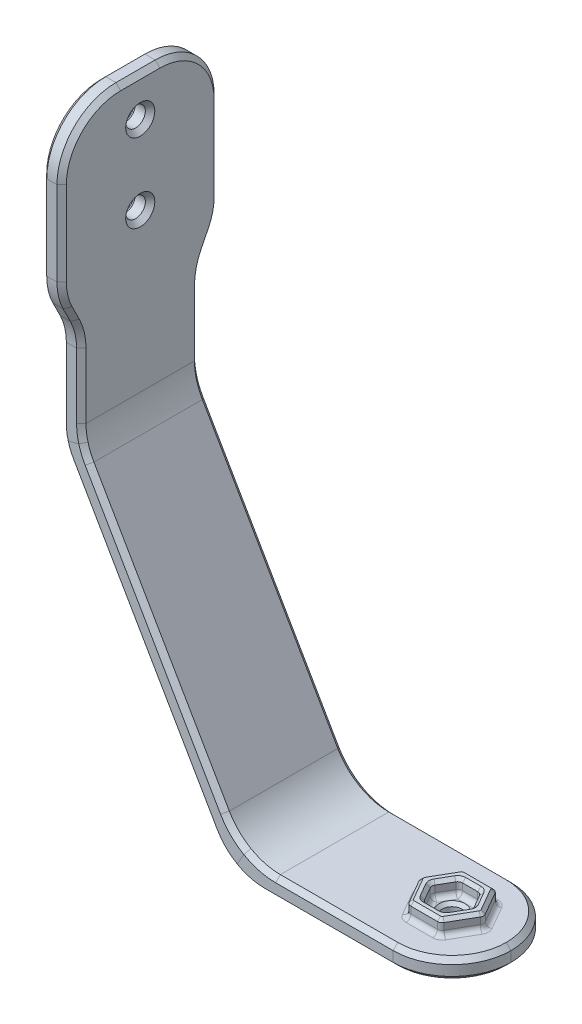
SolidWorks part; units mm, degrees
material "Onyx"
ref_plane "Front Plane" through (0, 0, 0) normal (0, 0, 1) x (1, 0, 0)
ref_plane "Top Plane" through (0, 0, 0) normal (0, 1, 0) x (1, 0, 0)
ref_plane "Right Plane" through (0, 0, 0) normal (1, 0, 0) x (0, 0, -1)
sketch "Sketch1" plane through (0, 0, 0) normal (0, 0, 1) x (1, 0, 0)
  line L0 (0, 0) -> (0, -47.5145)
  line L1 (0, -47.5145) -> (26.5798, -93.552)
  line L2 (26.5798, -93.552) -> (61.5048, -93.552)
  dimension "D1" = 47.5145
  dimension "D3" = 150
  dimension "D4" = 120
  dimension "D5" = 34.925
  dimension "D2" = 46.0375
sketch "Sketch2" plane through (0, 0, 0) normal (0, 1, 0) x (1, 0, 0)
  line L1 (-1.5875, -9.525) -> (1.5875, -9.525)
  line L2 (-1.5875, -9.525) -> (-1.5875, 9.525)
  line L3 (-1.5875, 9.525) -> (1.5875, 9.525)
  line L4 (1.5875, -9.525) -> (1.5875, 9.525)
  line L5 (-1.5875, -9.525) -> (1.5875, 9.525) construction
  line L6 (-1.5875, 9.525) -> (1.5875, -9.525) construction
  point P0 (0, 0)
  dimension "D1" = 3.175
  dimension "D2" = 19.05
sweep "Sweep1" add profiles "Sketch2" path "Sketch1"
sketch "Sketch7" plane through (0, 0, 0) normal (1, 0, 0) x (0, 0, -1)
  line L0 (-12.7, -25.4) -> (-9.525, -31.75)
  line L1 (-12.7, 0) -> (12.7, 0)
  line L2 (-12.7, 0) -> (-12.7, -25.4)
  line L3 (-12.7, -25.4) -> (12.7, -25.4) construction
  line L4 (12.7, 0) -> (12.7, -25.4)
  line L5 (-9.525, 0) -> (-9.525, -47.0892) construction
  line L6 (-9.525, -31.75) -> (9.525, -31.75)
  line L7 (9.525, 0) -> (9.525, -47.0892) construction
  line L8 (9.525, -31.75) -> (12.7, -25.4)
  dimension "D1" = 25.4
  dimension "D2" = 25.4
  dimension "D3" = 6.35
extrude "Boss-Extrude1" add sketch "Sketch7" along normal mid plane 3.175 contours L2 L0 L6 L8 L4 L1
sketch "Sketch8" plane through (0, 0, 0) normal (1, 0, 0) x (0, 0, -1)
  line L0 (0, -19.05) -> (0, -6.35) construction
  line L1 (0, -6.35) -> (0, 0) construction
  circle A0 centre (0, -6.35) radius 1.5875
  circle A1 centre (0, -19.05) radius 1.5875
  dimension "D1" = 3.175
  dimension "D2" = 6.35
  dimension "D3" = 12.7
extrude "Cut-Extrude1" cut sketch "Sketch8" against normal through all both and the other way through all
sketch "Sketch9" plane through (0, -91.9645, 0) normal (0, 1, 0) x (1, 0, 0)
  line L0 (61.5048, 0) -> (51.9798, 0) construction
  line L1 (61.5048, -9.525) -> (61.5048, 9.525) construction
  circle A0 centre (51.9798, 0) radius 1.5875
  dimension "D1" = 3.175
  dimension "D2" = 9.525
extrude "Cut-Extrude2" cut sketch "Sketch9" against normal through all both and the other way through all
sketch "Sketch10" plane through (0, -91.9645, 0) normal (0, 1, 0) x (1, 0, 0)
  line L1 (53.6662, 2.921) -> (50.2933, 2.921)
  line L2 (50.2933, 2.921) -> (48.6069, 0)
  line L3 (48.6069, 0) -> (50.2933, -2.921)
  line L4 (50.2933, -2.921) -> (53.6662, -2.921)
  line L5 (53.6662, -2.921) -> (55.3526, 0)
  line L6 (55.3526, 0) -> (53.6662, 2.921)
  line L7 (54.5827, 4.5085) -> (49.3768, 4.5085)
  line L8 (49.3768, 4.5085) -> (46.7738, 0)
  line L9 (46.7738, 0) -> (49.3768, -4.5085)
  line L10 (49.3768, -4.5085) -> (54.5827, -4.5085)
  line L11 (54.5827, -4.5085) -> (57.1857, 0)
  line L12 (57.1857, 0) -> (54.5827, 4.5085)
  circle A0 centre (51.9798, 0) radius 2.921 construction
  circle A1 centre (51.9798, 0) radius 4.5085 construction
  dimension "D1" = 5.842
  dimension "D2" = 1.5875
extrude "Boss-Extrude2" add sketch "Sketch10" along normal blind 2.3813
fillet "Fillet1" radius 9.525 12 edges at (0, -31.75, -9.525) (0, -25.4, -12.7) (0, -31.75, 9.525) (0, -25.4, 12.7) (0, 0, -12.7) (0, 0, 12.7) (61.5048, -93.552, -9.525) (61.5048, -93.552, 9.525) (1.5875, -47.0892, 0) (-1.5875, -47.9399, 0) (25.6632, -95.1395, 0) (27.4963, -91.9645, 0)
fillet "Fillet2" radius 0.7937 24 edges at (57.1857, -90.7739, 0) (54.5827, -90.7739, 4.5085) (46.7738, -90.7739, 0) (49.3768, -90.7739, -4.5085) (54.5827, -90.7739, -4.5085) (49.3768, -90.7739, 4.5085) (48.6069, -90.7739, 0) (50.2933, -90.7739, 2.921) (53.6662, -90.7739, 2.921) (55.3526, -90.7739, 0) (53.6662, -90.7739, -2.921) (50.2933, -90.7739, -2.921) (51.9798, -91.9645, 2.921) (49.4501, -91.9645, 1.4605) (49.4501, -91.9645, -1.4605) (54.5094, -91.9645, -1.4605) (54.5094, -91.9645, 1.4605) (51.9798, -91.9645, -2.921) (51.9798, -91.9645, -4.5085) (48.0753, -91.9645, -2.2543) (48.0753, -91.9645, 2.2543) (51.9798, -91.9645, 4.5085) (55.8842, -91.9645, -2.2543) (55.8842, -91.9645, 2.2542)
chamfer "Chamfer1" distance 0.762 angle 45 58 edges at (58.715, -95.1395, 6.7352) (58.715, -95.1395, -6.7352) (41.5711, -95.1395, 9.525) (41.5711, -95.1395, -9.525) (28.6972, -94.815, 9.525) (28.6972, -94.815, -9.525) (24.4273, -92.3497, 9.525) (24.4273, -92.3497, -9.525) (11.3011, -70.2636, 9.525) (11.3011, -70.2636, -9.525) (-0.8625, -49.0327, 9.525) (-0.8625, -49.0327, -9.525) (-1.506, -46.631, 9.525) (-1.506, -46.631, -9.525) (-1.5875, -39.6931, 9.525) (-1.5875, -31.8102, 9.7798) (-1.5875, -28.575, 11.1125) (-1.5875, -25.3398, 12.4452) (-1.5875, -16.3382, 12.7) (-1.5875, -2.7898, 9.9102) (-1.5875, 0, 0) (-1.5875, -2.7898, -9.9102) (-1.5875, -16.3382, -12.7) (-1.5875, -25.3398, -12.4452) (-1.5875, -28.575, -11.1125) (-1.5875, -31.8102, -9.7798) (-1.5875, -39.6931, -9.525) (-1.5875, -19.05, -1.5875) (-1.5875, -6.35, -1.5875) (58.715, -91.9645, -6.7352) (58.715, -91.9645, 6.7352) (42.4877, -91.9645, -9.525) (42.4877, -91.9645, 9.525) (30.5303, -91.64, -9.525) (30.5303, -91.64, 9.525) (26.2604, -89.1747, -9.525) (26.2604, -89.1747, 9.525) (13.8051, -68.2507, -9.525) (13.8051, -68.2507, 9.525) (2.3125, -48.182, -9.525) (2.3125, -48.182, 9.525) (1.669, -45.7802, -9.525) (1.669, -45.7802, 9.525) (1.5875, -39.2677, -9.525) (1.5875, -31.8102, -9.7798) (1.5875, -28.575, -11.1125) (1.5875, -25.3398, -12.4452) (1.5875, -16.3382, -12.7) (1.5875, -2.7898, -9.9102) (1.5875, 0, 0) (1.5875, -2.7898, 9.9102) (1.5875, -16.3382, 12.7) (1.5875, -25.3398, 12.4452) (1.5875, -28.575, 11.1125) (1.5875, -31.8102, 9.7798) (1.5875, -39.2677, 9.525) (1.5875, -20.6375, 0) (1.5875, -7.9375, 0)
chamfer "Chamfer2" distance 0.508 angle 45 26 edges at (53.5673, -91.9645, 0) (50.3923, -95.1395, 0) (50.3547, -89.5833, -2.8147) (49.4501, -89.5833, -1.4605) (48.7297, -89.5833, 0) (49.4501, -89.5833, 1.4605) (50.3547, -89.5833, 2.8147) (51.9798, -89.5833, 2.921) (53.6048, -89.5833, 2.8147) (54.5094, -89.5833, 1.4605) (55.2298, -89.5833, 0) (54.5094, -89.5833, -1.4605) (53.6048, -89.5833, -2.8147) (51.9798, -89.5833, -2.921) (54.5213, -89.5833, 4.4022) (51.9798, -89.5833, 4.5085) (49.4382, -89.5833, 4.4022) (48.0753, -89.5833, 2.2542) (46.8966, -89.5833, 0) (48.0753, -89.5833, -2.2542) (49.4382, -89.5833, -4.4022) (51.9798, -89.5833, -4.5085) (54.5213, -89.5833, -4.4022) (55.8842, -89.5833, -2.2543) (57.0629, -89.5833, 0) (55.8842, -89.5833, 2.2542)
equation "\"D1@Sketch1\"=1.25+0.1875+0.433151"
